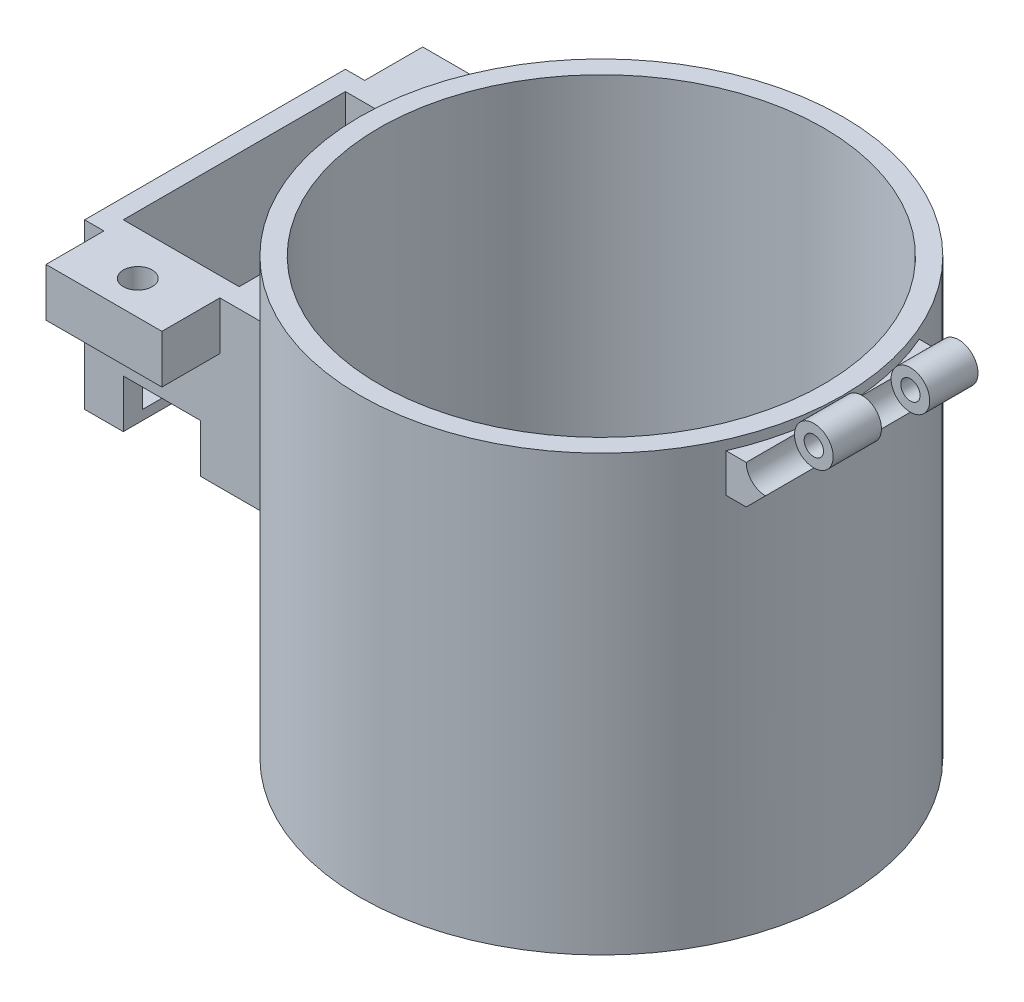
SolidWorks part; units mm, degrees
ref_plane "Front Plane" through (0, 0, 0) normal (0, 0, 1) x (1, 0, 0)
ref_plane "Top Plane" through (0, 0, 0) normal (0, 1, 0) x (1, 0, 0)
ref_plane "Right Plane" through (0, 0, 0) normal (1, 0, 0) x (0, 0, -1)
sketch "Sketch1" plane through (0, 0, 0) normal (0, 1, 0) x (1, 0, 0)
  circle A0 centre (0, 0) radius 25
  dimension "D1" = 50
extrude "Boss-Extrude1" add sketch "Sketch1" along normal blind 45
shell "Shell1" thickness 2 removed face at (0, 45, 25)
sketch "Sketch2" plane through (0, 2, 0) normal (0, 1, 0) x (1, 0, 0)
  line L0 (0, 0) -> (13.888, 0) construction
  line L1 (0, 0) -> (9.7749, 16.9307) construction
  circle A1 centre (15, 0) radius 3.5
  circle A2 centre (7.5, -12.9904) radius 3.5
  circle A3 centre (-7.5, -12.9904) radius 3.5
  circle A4 centre (-15, 0) radius 3.5
  circle A5 centre (-7.5, 12.9904) radius 3.5
  circle A6 centre (7.5, 12.9904) radius 3.5
  point P18 (0, 0)
  dimension "D1" = 7
  dimension "D2" = 15
  dimension "D4" = 60
  dimension "D5" = 15
  dimension "D3" = 6
extrude "Cut-Extrude1" cut sketch "Sketch2" against normal up to surface (2 mm away) up to face at (0, 0, 25)
sketch "Sketch3" plane through (0, 0, 0) normal (0, 0, 1) x (1, 0, 0)
  line L4 (25, 44) -> (25, 40)
  line L5 (25, 0) -> (25, 45) construction
  line L6 (25, 40) -> (27, 42)
  line L7 (25, 45) -> (-25, 45) construction
  arc A2 (27, 42) -> (25, 44) centre (27, 44) ccw
  dimension "D1" = 4
  dimension "D2" = 1
  dimension "D4" = 4
  dimension "D3" = 45
extrude "Boss-Extrude4" add sketch "Sketch3" along normal blind 10 and the other way blind 10 separate body
sketch "Sketch8" plane through (25, 0, 0) normal (-1, 0, 0) x (0, 0, 1)
  line L1 (10, 40) -> (-10, 40)
  line L2 (10, 40) -> (10, 44)
  line L3 (10, 44) -> (-10, 44)
  line L4 (-10, 40) -> (-10, 44)
extrude "Boss-Extrude6" add sketch "Sketch8" along normal up to surface up to face at (0, 45, 25)
sketch "Sketch9" plane through (0, 0, 10) normal (0, 0, 1) x (1, 0, 0)
  circle A0 centre (27, 44) radius 1
  dimension "D1" = 2
extrude "Cut-Extrude4" cut sketch "Sketch9" against normal through all both and the other way through all
sketch "Sketch10" plane through (0, 0, 10) normal (0, 0, 1) x (1, 0, 0)
  circle A0 centre (27, 44) radius 2
extrude "Cut-Extrude5" cut sketch "Sketch10" against normal blind 5
pattern_linear "LPattern2" count 2 spacing 10 along (0, 0, -1) of "Cut-Extrude5"
ref_plane "Plane1" through (-25, 0, 0) normal (1, 0, 0) x (0, 0, -1)
sketch "Sketch11" plane through (-25, 0, 0) normal (1, 0, 0) x (0, 0, -1)
  line L1 (13.5, 35) -> (-13.5, 35)
  line L2 (13.5, 35) -> (13.5, 18)
  line L3 (13.5, 18) -> (-13.5, 18)
  line L4 (-13.5, 35) -> (-13.5, 18)
  line L5 (25, 45) -> (-25, 45) construction
  point P4 (0, 18)
  dimension "D1" = 27
  dimension "D2" = 17
  dimension "D3" = 10
extrude "Boss-Extrude7" add sketch "Sketch11" against normal blind 15 and the other way up to surface separate body other way up to face at (0, 45, 25)
sketch "Sketch12" plane through (0, 35, 0) normal (0, 1, 0) x (1, 0, 0)
  line L0 (-40, 13.5) -> (-40, -13.5) construction
  line L1 (-38, 11.5) -> (-26, 11.5)
  line L2 (-38, 11.5) -> (-38, -11.5)
  line L3 (-38, -11.5) -> (-26, -11.5)
  line L4 (-26, 11.5) -> (-26, -11.5)
  point P6 (-40, 0)
  point P7 (-38, 0)
  dimension "D1" = 23
  dimension "D2" = 12
  dimension "D3" = 2
extrude "Cut-Extrude6" cut sketch "Sketch12" against normal blind 16
sketch "Sketch13" plane through (0, 0, 13.5) normal (0, 0, 1) x (1, 0, 0)
  line L0 (-40, 35) -> (-21.0416, 35) construction
  line L1 (-38, 35) -> (-26, 35)
  line L2 (-38, 35) -> (-38, 30)
  line L3 (-38, 30) -> (-26, 30)
  line L4 (-26, 35) -> (-26, 30)
  point P6 (0, 0)
  point P7 (0, 0)
  point P10 (0, 0)
  dimension "D1" = 5
extrude "Boss-Extrude8" add sketch "Sketch13" along normal blind 6
sketch "Sketch14" plane through (0, 35, 0) normal (0, 1, 0) x (1, 0, 0)
  line L0 (-38, -11.5) -> (-26, -11.5) construction
  line L1 (-26, -19.5) -> (-38, -19.5) construction
  circle A0 centre (-32, -16) radius 1.5
  point P4 (-32, -11.5)
  dimension "D1" = 3
  dimension "D2" = 3.5
extrude "Cut-Extrude7" cut sketch "Sketch14" against normal up to surface (5 mm away) up to face at (-32, 30, 16.5)
mirror "Mirror1" about plane through (0, 0, 0) normal (0, 0, 1) of "Boss-Extrude8", "Cut-Extrude7"
sketch "Sketch15" plane through (0, 0, -13.5) normal (0, 0, -1) x (-1, 0, 0)
  line L0 (40, 18) -> (21.0416, 18) construction
  line L1 (28, 18) -> (36, 18)
  line L2 (28, 18) -> (28, 23)
  line L3 (28, 23) -> (36, 23)
  line L4 (36, 18) -> (36, 23)
  line L5 (26, 35) -> (38, 35) construction
  point P8 (32, 35)
  point P9 (32, 23)
  dimension "D1" = 8
  dimension "D2" = 5
extrude "Cut-Extrude8" cut sketch "Sketch15" against normal up to surface (27 mm away) up to face at (-31.2604, 29.5, 13.5)
